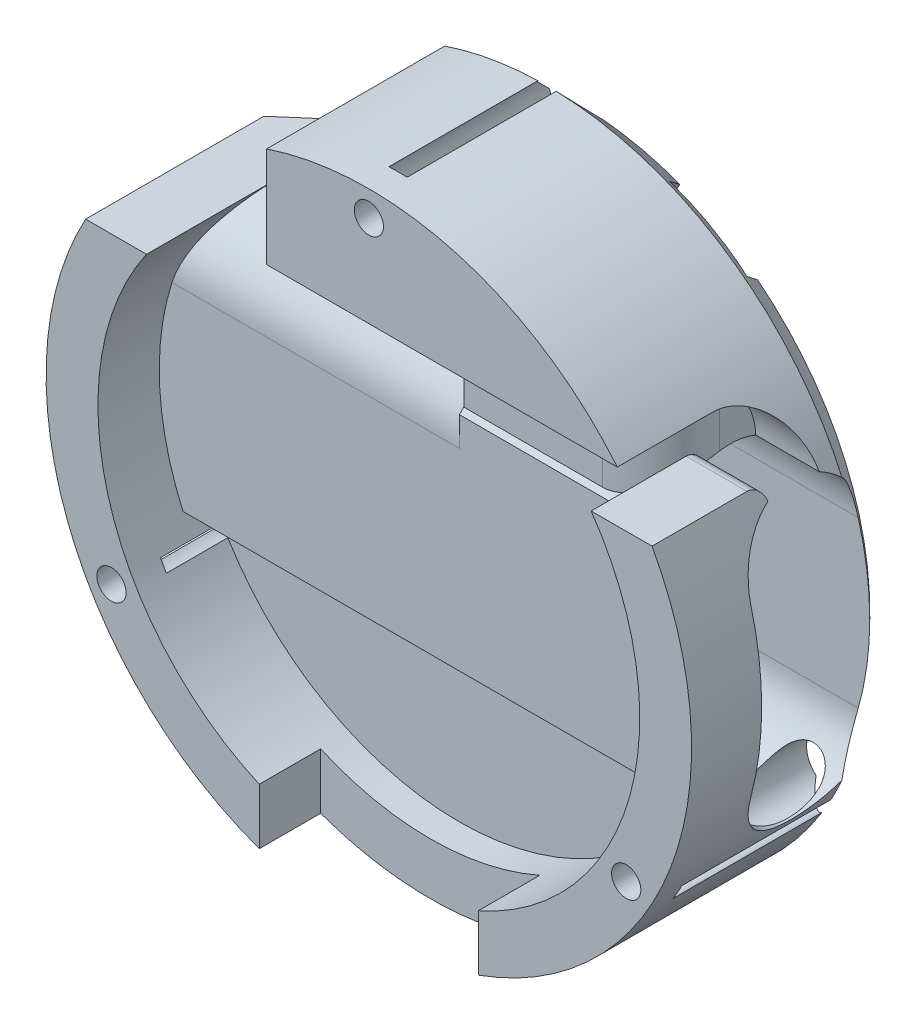
SolidWorks part; units mm, degrees
ref_plane "正面" through (0, 0, 0) normal (0, 0, 1) x (1, 0, 0)
ref_plane "平面" through (0, 0, 0) normal (0, 1, 0) x (1, 0, 0)
ref_plane "右側面" through (0, 0, 0) normal (1, 0, 0) x (0, 0, -1)
sketch "ｽｹｯﾁ1" plane through (0, 0, 0) normal (0, 0, 1) x (1, 0, 0)
  circle A0 centre (0, 0) radius 22.1
  dimension "D1" = 44.2
extrude "ﾎﾞｽ - 押し出し1" add sketch "ｽｹｯﾁ1" against normal blind 10
sketch "ｽｹｯﾁ2" plane through (0, 0, 0) normal (1, 0, 0) x (0, -1, 0)
  line L0 (5.65, 5.05) -> (-5.65, 5.05) construction
  line L1 (5.65, 0.8) -> (-5.65, 0.8) construction
  line L2 (5.65, 9.3) -> (-5.65, 9.3) construction
  line L3 (5.65, 0.6) -> (-5.65, 0.6)
  line L4 (5.65, 9.5) -> (-5.65, 9.5)
  line L5 (-22.1, 0) -> (22.1, 0) construction
  arc A0 (5.65, 0.8) -> (5.65, 9.3) centre (5.65, 5.05) ccw construction
  arc A1 (-5.65, 9.3) -> (-5.65, 0.8) centre (-5.65, 5.05) ccw construction
  arc A2 (-5.65, 9.5) -> (-5.65, 0.6) centre (-5.65, 5.05) ccw
  arc A3 (5.65, 0.6) -> (5.65, 9.5) centre (5.65, 5.05) ccw
  point P2 (0, 5.05)
  dimension "D2" = 11.3
  dimension "D1" = 8.5
  dimension "D3" = 0.2
  dimension "D4" = 0.6
extrude "ｶｯﾄ - 押し出し1" cut sketch "ｽｹｯﾁ2" against normal blind 15.5 and the other way through all
sketch "ｽｹｯﾁ8" plane through (-15.5, 0, 0) normal (1, 0, 0) x (0, 0, -1)
  line L0 (9.5, -5.65) -> (9.5, 5.65) construction
  line L1 (0.6, -5.65) -> (0.6, 5.65) construction
  circle A0 centre (5.05, 0) radius 4.45
extrude "ｶｯﾄ - 押し出し7" cut sketch "ｽｹｯﾁ8" against normal through all
sketch "ｽｹｯﾁ9" plane through (0, 0, -10) normal (0, 0, -1) x (-1, 0, 0)
  line L0 (8, 14.1) -> (-8, 14.1)
  line L1 (8, 14) -> (-8, 14) construction
  line L2 (9, 13) -> (9, -2) construction
  line L3 (8, -3) -> (-8, -3) construction
  line L4 (-9, 13) -> (-9, -2) construction
  line L5 (9, 14) -> (-9, -3) construction
  line L6 (9, -3) -> (-9, 14) construction
  line L7 (-9.1, 13) -> (-9.1, -2)
  line L8 (8, -3.1) -> (-8, -3.1)
  line L9 (9.1, 13) -> (9.1, -2)
  line L10 (8, 15.1) -> (-8, 15.1)
  line L11 (-10.1, 13) -> (-10.1, -2)
  line L12 (8, -4.1) -> (-8, -4.1)
  line L13 (10.1, 13) -> (10.1, -2)
  arc A0 (9, -2) -> (8, -3) centre (8, -2) cw construction
  arc A1 (-9, -2) -> (-8, -3) centre (-8, -2) ccw construction
  arc A2 (9, 13) -> (8, 14) centre (8, 13) ccw construction
  arc A3 (-8, 14) -> (-9, 13) centre (-8, 13) ccw construction
  arc A4 (-8, 14.1) -> (-9.1, 13) centre (-8, 13) ccw
  arc A5 (-9.1, -2) -> (-8, -3.1) centre (-8, -2) ccw
  arc A6 (9.1, -2) -> (8, -3.1) centre (8, -2) cw
  arc A7 (9.1, 13) -> (8, 14.1) centre (8, 13) ccw
  arc A8 (-8, 15.1) -> (-10.1, 13) centre (-8, 13) ccw
  arc A9 (-10.1, -2) -> (-8, -4.1) centre (-8, -2) ccw
  arc A10 (10.1, -2) -> (8, -4.1) centre (8, -2) cw
  arc A11 (10.1, 13) -> (8, 15.1) centre (8, 13) ccw
  point P0 (0, 5.5)
  dimension "D3" = 1
  dimension "D1" = 18
  dimension "D2" = 17
  dimension "D4" = 5.5
  dimension "D5" = 0.1
  dimension "D6" = 1
extrude "ﾎﾞｽ - 押し出し3" add sketch "ｽｹｯﾁ9" along normal blind 2.7 contours L11 A9 L12 A10 L13 A11 L10 A8
sketch "ｽｹｯﾁ16" plane through (0, 0, -10) normal (0, 0, 1) x (1, 0, 0)
  circle A0 centre (0, 0) radius 12.55
  circle A1 centre (0, 0) radius 13.55
  dimension "D1" = 25.1
  dimension "D2" = 1
extrude "ﾎﾞｽ - 押し出し4" add sketch "ｽｹｯﾁ16" against normal offset from surface (3.7 mm away) 1 contours A1 up to face at (0, 5.5, -12.7) offset beyond the face yes
extrude "ｶｯﾄ - 押し出し13" cut sketch "ｽｹｯﾁ9<3>" along normal through all contours L0 A4 L7 A5 L8 A6 L9 A7
sketch "ｽｹｯﾁ9<3>" plane through (0, 0, -10) normal (0, 0, -1) x (-1, 0, 0) same geometry as "ｽｹｯﾁ9"
extrude "ｶｯﾄ - 押し出し14" cut sketch "ｽｹｯﾁ16<3>" against normal through all from surface contours A0 starting at face at (0, 12.4914, -12.7)
sketch "ｽｹｯﾁ16<3>" plane through (0, 0, -10) normal (0, 0, 1) x (1, 0, 0) same geometry as "ｽｹｯﾁ16"
sketch "ｽｹｯﾁ3" plane through (0, 0, 0) normal (0, 0, 1) x (1, 0, 0)
  line L0 (9.722, 17.2489) -> (0, 0) construction
  line L1 (7.845, 20.0286) -> (13.072, 17.0826)
  line L2 (7.845, 20.0286) -> (6.372, 17.4152)
  line L3 (6.372, 17.4152) -> (11.5989, 14.4691)
  line L4 (13.072, 17.0826) -> (11.5989, 14.4691)
  line L5 (7.845, 20.0286) -> (11.5989, 14.4691) construction
  line L6 (6.372, 17.4152) -> (13.072, 17.0826) construction
  line L7 (11.7427, 10.6) -> (2.9876, 15.5346)
  line L8 (11.7427, 10.6) -> (13.363, 13.4748)
  line L9 (13.363, 13.4748) -> (4.6079, 18.4094)
  line L10 (2.9876, 15.5346) -> (4.6079, 18.4094)
  line L11 (11.7427, 10.6) -> (4.6079, 18.4094) construction
  line L12 (13.363, 13.4748) -> (2.9876, 15.5346) construction
  line L16 (-2.7117, 10.6) -> (22.8086, 10.6) construction
  line L17 (0, 5.65) -> (0, 10.1) construction
  line L18 (0, 5.65) -> (0, 10.1)
  circle A0 centre (0, 0) radius 22.1 construction
  point P0 (9.722, 17.2489)
  point P5 (8.1753, 14.5047)
  dimension "D1" = 6
  dimension "D2" = 3
  dimension "D3" = 10.05
  dimension "D4" = 3.3
  dimension "D5" = 0.8
  dimension "D6" = 0.5
ref_plane "平面1" through (10.4585, 18.5556, 0) normal (-0.491, -0.8712, 0) x (0.8712, -0.491, 0)
sketch "ｽｹｯﾁ5" plane through (10.4585, 18.5556, 0) normal (-0.491, -0.8712, 0) x (0.8712, -0.491, 0)
  line L0 (-3, 0) -> (3, 0) construction
  line L1 (-3, 0) -> (3, 0) construction
  line L3 (22.1, 0) -> (-22.1, 0) construction
  line L4 (-22.1, -10) -> (22.1, -10) construction
  line L6 (-3.05, -6) -> (-3.05, -10)
  line L7 (-3.05, -10) -> (3.05, -10)
  line L8 (3.05, -6) -> (3.05, -10)
  arc A0 (3.05, -6) -> (-3.05, -6) centre (0, -6) ccw
  dimension "D1" = 6
  dimension "D2" = 0.05
extrude "ｶｯﾄ - 押し出し4" cut sketch "ｽｹｯﾁ5" along normal up to vertex (3 mm away) up to point (11.5989, 14.4691, 0)
sketch "ｽｹｯﾁ6" plane through (8.9855, 15.9421, 0) normal (0.491, 0.8712, 0) x (0.8712, -0.491, 0)
  line L2 (-5.025, 6) -> (-5.025, 14.5619)
  line L3 (-5.025, 14.5619) -> (5.025, 14.5619)
  line L4 (5.025, 6) -> (5.025, 14.5619)
  line L5 (5.025, 0) -> (-5.025, 0) construction
  line L6 (5.025, 0) -> (-5.025, 0)
  arc A0 (-5.025, 6) -> (5.025, 6) centre (0, 6) ccw
  arc A1 (-3.05, 6) -> (3.05, 6) centre (0, 6) ccw construction
extrude "ｶｯﾄ - 押し出し5" cut sketch "ｽｹｯﾁ6" against normal up to vertex (3.3 mm away) contours L3 L4 A0 L2 up to point (2.9876, 15.5346, 0)
pattern_circular "円形ﾊﾟﾀｰﾝ1" count 2 over 360 about axis through (0, 0, -10) along (0, 0, 1) of "ｶｯﾄ - 押し出し4" reverse direction yes
sketch "ｽｹｯﾁ4" plane through (0, 0, 0) normal (0, 0, 1) x (1, 0, 0)
  line L0 (-2.7117, 10.6) -> (22.8086, 10.6) construction
  line L5 (2, 10.6) -> (-20.73, 10.6)
  line L6 (2, 10.6) -> (2, 14.1)
  line L7 (2, 14.1) -> (-20.73, 14.1)
  line L8 (-20.73, 10.6) -> (-20.73, 14.1)
  line L10 (-20.73, 14.1) -> (-7, 14.1)
  line L11 (-20.73, 14.1) -> (-20.73, 21.1195)
  line L12 (-20.73, 21.1195) -> (-7, 21.1195)
  line L13 (-7, 14.1) -> (-7, 21.1195)
  circle A0 centre (0, 0) radius 22.1 construction
  dimension "D2" = 8
  dimension "D1" = 2
  dimension "D3" = 7
  dimension "D4" = 10.6
extrude "ｶｯﾄ - 押し出し3" cut sketch "ｽｹｯﾁ4" against normal through all contours L6 L5 L8 L7 | L11 L10 L13 L12
sketch "ｽｹｯﾁ10" plane through (0, 0, 0) normal (0, 0, 1) x (1, 0, 0)
  line L0 (-7, 14.1) -> (12.0537, 14.1)
  line L4 (2, 14.1) -> (-7, 14.1) construction
  line L5 (2, 10.6) -> (-19.392, 10.6) construction
  line L14 (0, -14.3466) -> (0, -25.0856) construction
  line L15 (-7.5, -20.7885) -> (-7.5, -16.9662)
  line L16 (2, 14.1) -> (2, 10.6)
  line L17 (7.5, -16.9662) -> (7.5, -20.7885)
  line L18 (2, 10.6) -> (-19.392, 10.6)
  line L19 (-15.2231, 10.6) -> (-19.392, 10.6)
  line L20 (-7, 20.9621) -> (-7, 14.1)
  line L21 (-7, 20.9621) -> (-7, 14.1)
  line L22 (-7, 14.1) -> (2, 14.1)
  arc A1 (-19.392, 10.6) -> (-7, 20.9621) centre (0, 0) ccw
  arc A2 (-19.392, 10.6) -> (-7.5, -20.7885) centre (0, 0) ccw
  arc A3 (12.0537, 14.1) -> (7.5, -16.9662) centre (0, 0) cw
  arc A4 (-7.5, -16.9662) -> (-15.2231, 10.6) centre (0, 0) cw
  arc A5 (7.5, -20.7885) -> (-7, 20.9621) centre (0, 0) ccw
  arc A6 (7.5, -20.7885) -> (-7, 20.9621) centre (0, 0) ccw
  dimension "D2" = 3.55
  dimension "D4" = 15
  dimension "D3" = 19.0537
  dimension "D1" = 0
extrude "ﾎﾞｽ - 押し出し2" add sketch "ｽｹｯﾁ10" along normal blind 4.2 contours L19 A2 L15 A4 | L21 L0 A3 L17 A5
sketch "ｽｹｯﾁ12" plane through (0, 0, 0) normal (0, 0, 1) x (1, 0, 0)
  circle A7 centre (0, 20.35) radius 0.9 construction
  circle A8 centre (0, 20.35) radius 1
  circle A10 centre (17.6236, -10.175) radius 0.9 construction
  circle A11 centre (17.6236, -10.175) radius 1
  circle A12 centre (-17.6236, -10.175) radius 0.9 construction
  circle A14 centre (-17.6236, -10.175) radius 1
  dimension "D1" = 2
extrude "ｶｯﾄ - 押し出し8" cut sketch "ｽｹｯﾁ12" against normal through all both and the other way through all
sketch "ｽｹｯﾁ13" plane through (0, 0, 0) normal (0, 0, 1) x (1, 0, 0)
  circle A0 centre (0, 20.35) radius 1.85
  circle A1 centre (17.6236, -10.175) radius 1.85
  circle A2 centre (-17.6236, -10.175) radius 1.85
  dimension "D1" = 3.7
extrude "ｶｯﾄ - 押し出し10" cut sketch "ｽｹｯﾁ13" against normal through all and the other way offset from surface 2 other way up to face at (-16.6236, -10.175, 4.2)
sketch "ｽｹｯﾁ14" plane through (0, 0, 4.2) normal (0, 0, 1) x (1, 0, 0)
  line L0 (2, 14.1) -> (17.0176, 14.1)
  line L1 (-7, 14.1) -> (12.0537, 14.1) construction
  line L2 (2, 10.6) -> (19.392, 10.6)
  line L3 (2, 10.6) -> (-15.2231, 10.6) construction
  line L4 (2, 10.6) -> (2, 14.1) construction
  line L5 (2, 14.1) -> (2, 10.6)
  arc A0 (-19.392, 10.6) -> (-7.5, -20.7885) centre (0, 0) ccw construction
  arc A3 (19.392, 10.6) -> (17.0176, 14.1) centre (0, 0) ccw
extrude "ｶｯﾄ - 押し出し11" cut sketch "ｽｹｯﾁ14" against normal up to surface (4.2 mm away) up to face at (0.1782, -5.4044, 0)
sketch "ｽｹｯﾁ15" plane through (0, 0, 0) normal (1, 0, 0) x (0, 0, -1)
  line L0 (0, 14.1) -> (0, 10.6)
  line L1 (0, 10.6) -> (2.3, 10.6)
  line L2 (3.3, 9.6) -> (3.3, 9.7415)
  line L3 (3.3, 9.7415) -> (6.8, 9.7415)
  line L4 (6.8, 9.7415) -> (6.8, 9.6)
  line L5 (2.3, 14.1) -> (0, 14.1)
  arc A0 (9.5, 5.65) -> (0.6, 5.65) centre (5.05, 5.65) ccw construction
  arc A1 (9.5, 5.65) -> (0.6, 5.65) centre (5.05, 5.65) ccw construction
  arc A2 (6.8, 9.6) -> (2.3, 14.1) centre (2.3, 9.6) ccw
  arc A3 (3.3, 9.6) -> (2.3, 10.6) centre (2.3, 9.6) ccw
  point P21 (3.3, 10.6)
  dimension "D1" = 1
extrude "ｶｯﾄ - 押し出し12" cut sketch "ｽｹｯﾁ15" along normal through all from offset 15.5 contours A3 L2 L3 A2 L5 L0 L1 region at (0, 11.8997, -3.1566)
fillet "ﾌｨﾚｯﾄ4" radius 3 1 edges at (2, 12.35, -10)
fillet "ﾌｨﾚｯﾄ5" radius 3 1 edges at (-1.6206, 15.1, -10)
mirror "ﾐﾗｰ1" about plane through (0, 0, 0) normal (1, 0, 0) of "円形ﾊﾟﾀｰﾝ1"
fillet "ﾌｨﾚｯﾄ6" [suppressed] radius 3
chamfer "面取り1" distance 2 angle 45 4 edges at (-3.8542, 21.7613, -10) (19.1392, 11.05, -10) (-22.0999, 0.0546, -10) (0, -22.1, -10)
fillet "ﾌｨﾚｯﾄ7" radius 5 1 edges at (-6.6115, 10.6, 0)
sketch "ｽｹｯﾁ18" plane through (0, 0, 0) normal (0, 0, 1) x (1, 0, 0)
  line L0 (-15.2231, -10.6) -> (15.2231, -10.6)
  line L1 (-24.6288, 0) -> (23.1084, 0) construction
  line L2 (-15.2231, 10.6) -> (2, 10.6) construction
  line L3 (-15.2231, 10.6) -> (2, 10.6) construction
  arc A0 (-15.2231, -10.6) -> (15.2231, -10.6) centre (0, 0) ccw
  arc A1 (-15.2231, 10.6) -> (-7.5, -16.9662) centre (0, 0) ccw construction
extrude "ｶｯﾄ - 押し出し15" cut sketch "ｽｹｯﾁ18" against normal blind 2
sketch "ｽｹｯﾁ19" plane through (0, 0, 0) normal (0, 0, 1) x (1, 0, 0)
  line L0 (-15.2231, 10.6) -> (2, 10.6) construction
  circle A0 centre (-12.392, 10.6) radius 1.5
  dimension "D1" = 3
  dimension "D2" = 7
extrude "ｶｯﾄ - 押し出し16" [suppressed] cut sketch "ｽｹｯﾁ19" against normal through all
extrude "ｶｯﾄ - 押し出し18" cut sketch "ｽｹｯﾁ14<2>" against normal blind 4.5 contours L2 A3 L0 L5
sketch "ｽｹｯﾁ14<2>" plane through (0, 0, 4.2) normal (0, 0, 1) x (1, 0, 0) same geometry as "ｽｹｯﾁ14"
fillet "ﾌｨﾚｯﾄ2" radius 4 1 edges at (15.5, 12.35, -0.3)
chamfer "面取り2" distance 3 angle 45 2 edges at (0, -10.6, 0) (8.6115, 10.6, 0)
equation "\"D2@ｽｹｯﾁ10\"=(44.2-38.7)/2 + 0.8"
